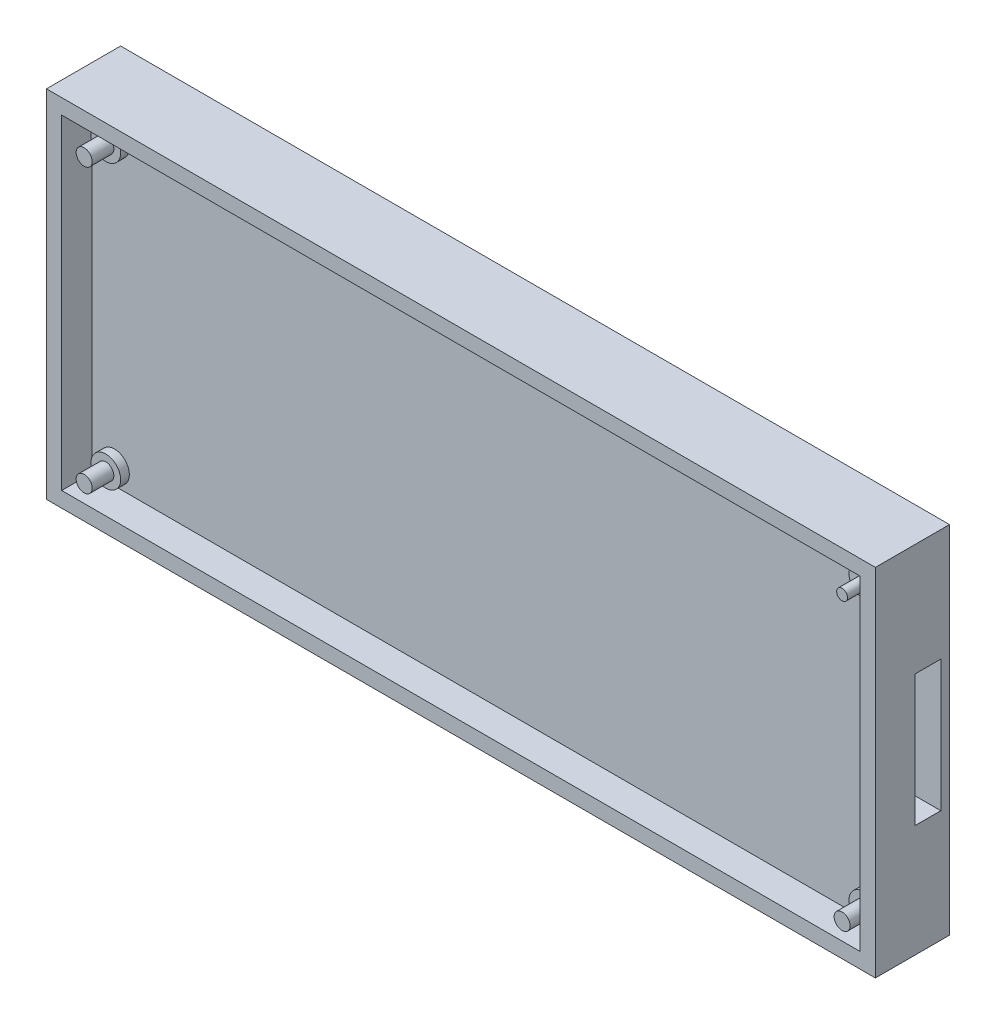
SolidWorks part; units mm, degrees
ref_plane "Front Plane" through (0, 0, 0) normal (0, 0, 1) x (1, 0, 0)
ref_plane "Top Plane" through (0, 0, 0) normal (0, 1, 0) x (1, 0, 0)
ref_plane "Right Plane" through (0, 0, 0) normal (1, 0, 0) x (0, 0, -1)
sketch "Sketch1" plane through (0, 0, 0) normal (0, 0, 1) x (1, 0, 0)
  line L1 (-101.6249, 55.2181) -> (80.9503, 55.2181)
  line L2 (-101.6249, 55.2181) -> (-101.6249, -18.2387)
  line L3 (-101.6249, -18.2387) -> (80.9503, -18.2387)
  line L4 (80.9503, 55.2181) -> (80.9503, -18.2387)
extrude "Boss-Extrude1" add sketch "Sketch1" along normal blind 5 and the other way blind 0.0932
sketch "Sketch2" plane through (0, 0, 5) normal (0, 0, 1) x (1, 0, 0)
  circle A0 centre (-97.9419, 50.9509) radius 3.4164
  circle A1 centre (76.8101, 50.9509) radius 3.4164
  circle A2 centre (76.8101, -14.2763) radius 3.4164
  circle A3 centre (-97.9419, -14.2763) radius 3.4164
extrude "Boss-Extrude2" add sketch "Sketch2" along normal blind 7
sketch "Sketch3" plane through (0, 0, 12) normal (0, 0, 1) x (1, 0, 0)
  circle A0 centre (-97.9419, 50.9509) radius 1.85
  circle A1 centre (-97.9419, -14.2763) radius 1.85
  circle A2 centre (76.8101, -14.2763) radius 1.85
  circle A3 centre (76.8101, 50.9509) radius 1.25
  dimension "D1" = 2.5
extrude "Boss-Extrude3" add sketch "Sketch3" along normal blind 5
sketch "Sketch4" plane through (0, 0, 5) normal (0, 0, 1) x (1, 0, 0)
  line L0 (-101.6249, 55.2181) -> (-106.6249, 60.2181) construction
  line L1 (80.9503, 55.2181) -> (-101.6249, 55.2181) construction
  line L2 (-101.6249, 55.2181) -> (-101.6249, -18.2387) construction
  line L3 (80.9503, -18.2387) -> (84.4858, -21.7743) construction
  line L4 (80.9503, -18.2387) -> (80.9503, 55.2181) construction
  line L5 (-101.6249, -18.2387) -> (80.9503, -18.2387) construction
  line L7 (-106.6249, 60.2181) -> (84.4858, 60.2181)
  line L8 (-106.6249, 60.2181) -> (-106.6249, -21.7743)
  line L9 (-106.6249, -21.7743) -> (84.4858, -21.7743)
  line L10 (84.4858, 60.2181) -> (84.4858, -21.7743)
  line L11 (-101.6249, 55.2181) -> (80.9503, 55.2181)
  line L12 (-101.6249, 55.2181) -> (-101.6249, -18.2387)
  line L13 (-101.6249, -18.2387) -> (80.9503, -18.2387)
  line L14 (80.9503, 55.2181) -> (80.9503, -18.2387)
  dimension "D1" = 5
  dimension "D2" = 135
  dimension "D3" = 5
  dimension "D4" = 135
extrude "Boss-Extrude4" add sketch "Sketch4" along normal up to surface (12 mm away) separate body up to face at (-96.0919, -14.2763, 17)
sketch "Sketch5" plane through (0, 0, 5) normal (0, 0, -1) x (-1, 0, 0)
  line L0 (-84.4858, -21.7743) -> (-84.4858, 60.2181) construction
  line L1 (-84.4858, 60.2181) -> (106.6249, 60.2181)
  line L2 (-84.4858, 60.2181) -> (-84.4858, -21.7743)
  line L3 (-84.4858, -21.7743) -> (106.6249, -21.7743)
  line L4 (106.6249, 60.2181) -> (106.6249, -21.7743)
  line L5 (-84.4858, 60.2181) -> (106.6249, 60.2181) construction
  line L6 (106.6249, -21.7743) -> (-84.4858, -21.7743) construction
extrude "Boss-Extrude5" add sketch "Sketch5" along normal up to surface (5.0932 mm away) up to face at (-10.3373, 18.4897, -0.0932)
sketch "Sketch6" plane through (0, 0, -0.0932) normal (0, 0, -1) x (-1, 0, 0)
  line L0 (-84.4858, 60.2181) -> (-84.4858, 19.2219) construction
  line L1 (-84.4858, 60.2181) -> (106.6249, 60.2181) construction
  line L2 (-84.4858, -21.7743) -> (-84.4858, 60.2181) construction
  line L3 (-84.4858, 34.3607) -> (-84.4858, 4.0831)
  line L7 (-56.8643, 4.0831) -> (-56.8643, 34.3607)
  line L10 (-66.23, 4.0831) -> (-66.23, 0.2715)
  line L11 (-66.23, 0.2715) -> (-63.5106, 0.2715)
  line L12 (-63.5106, 0.2715) -> (-56.8643, 4.0831)
  line L13 (-56.8643, 19.2219) -> (-67.8812, 19.2219) construction
  line L14 (-63.5106, 38.1723) -> (-56.8643, 34.3607)
  line L15 (-66.23, 38.1723) -> (-63.5106, 38.1723)
  line L16 (-66.23, 34.3607) -> (-66.23, 38.1723)
  line L17 (-66.23, 34.3607) -> (-84.4858, 34.3607)
  line L18 (-66.23, 4.0831) -> (-84.4858, 4.0831)
sketch "Sketch7" plane through (0, 0, 5) normal (0, 0, 1) x (1, 0, 0)
  line L0 (-101.6249, 55.2181) -> (-101.6249, -18.2387) construction
  line L1 (-101.6249, 55.2181) -> (80.9503, 55.2181)
  line L2 (-101.6249, 55.2181) -> (-101.6249, -18.2387)
  line L3 (-101.6249, -18.2387) -> (80.9503, -18.2387)
  line L4 (80.9503, 55.2181) -> (80.9503, -18.2387)
  line L5 (80.9503, 55.2181) -> (-101.6249, 55.2181) construction
  line L6 (-101.6249, -18.2387) -> (80.9503, -18.2387) construction
extrude "Boss-Extrude7" add sketch "Sketch7" along normal blind 5
extrude "Cut-Extrude1" cut sketch "Sketch6" against normal blind 6 from offset 2 offset against normal yes
ref_plane "Plane1" through (-11.0695, 0, 0) normal (1, 0, 0) x (0, 0, -1)
mirror "Mirror1" about plane through (-11.0695, 0, 0) normal (1, 0, 0) of "Cut-Extrude1"
ref_plane "Plane2" through (-101.6249, 55.2181, 17) normal (0, -1, 0) x (-1, 0, 0)
sketch "Sketch9" plane through (0, 0, 17) normal (0, 0, 1) x (1, 0, 0)
  line L0 (-101.6249, -18.2387) -> (80.9503, -18.2387) construction
  line L1 (-101.6249, 55.2181) -> (-103.1249, 55.2181)
  line L2 (-101.6249, 55.2181) -> (-101.6249, -18.2387)
  line L3 (-101.6249, -18.2387) -> (-103.1249, -18.2387)
  line L4 (-103.1249, 55.2181) -> (-103.1249, -18.2387)
  dimension "D1" = 1.5
extrude "Cut-Extrude2" cut sketch "Sketch9" against normal up to surface (7 mm away) up to face at (-10.3373, 18.4897, 10)
sketch "Sketch11" plane through (0, 0, 17) normal (0, 0, 1) x (1, 0, 0)
  line L0 (80.9503, -18.2387) -> (80.9503, 55.2181) construction
  line L1 (-103.1249, 55.2181) -> (80.9503, 55.2181)
  line L2 (-103.1249, 55.2181) -> (-103.1249, 56.7181)
  line L3 (-103.1249, 56.7181) -> (80.9503, 56.7181)
  line L4 (80.9503, 55.2181) -> (80.9503, 56.7181)
  dimension "D1" = 1.5
extrude "Cut-Extrude3" cut sketch "Sketch11" against normal up to surface (7 mm away) up to face at (-11.0873, 18.4897, 10)
